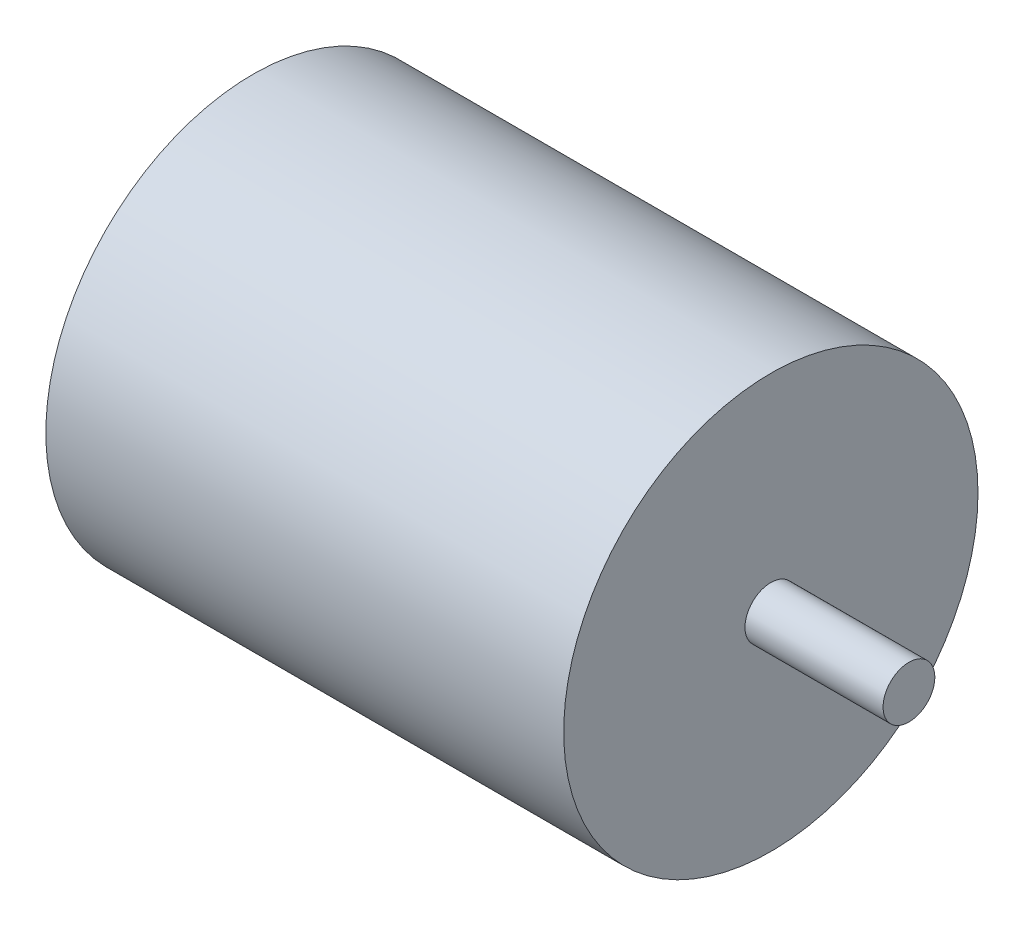
SolidWorks part; units mm, degrees
ref_plane "前视基准面" through (0, 0, 0) normal (0, 0, 1) x (1, 0, 0)
ref_plane "上视基准面" through (0, 0, 0) normal (0, 1, 0) x (1, 0, 0)
ref_plane "右视基准面" through (0, 0, 0) normal (1, 0, 0) x (0, 0, -1)
sketch "草图1" plane through (0, 0, 0) normal (1, 0, 0) x (0, 0, -1)
  circle A0 centre (0, 0) radius 12
extrude "凸台-拉伸1" add sketch "草图1" along normal blind 30
sketch "草图2" plane through (30, 0, 0) normal (1, 0, 0) x (0, 0, -1)
  circle A0 centre (0, 0) radius 1.5
extrude "凸台-拉伸2" add sketch "草图2" along normal blind 8
